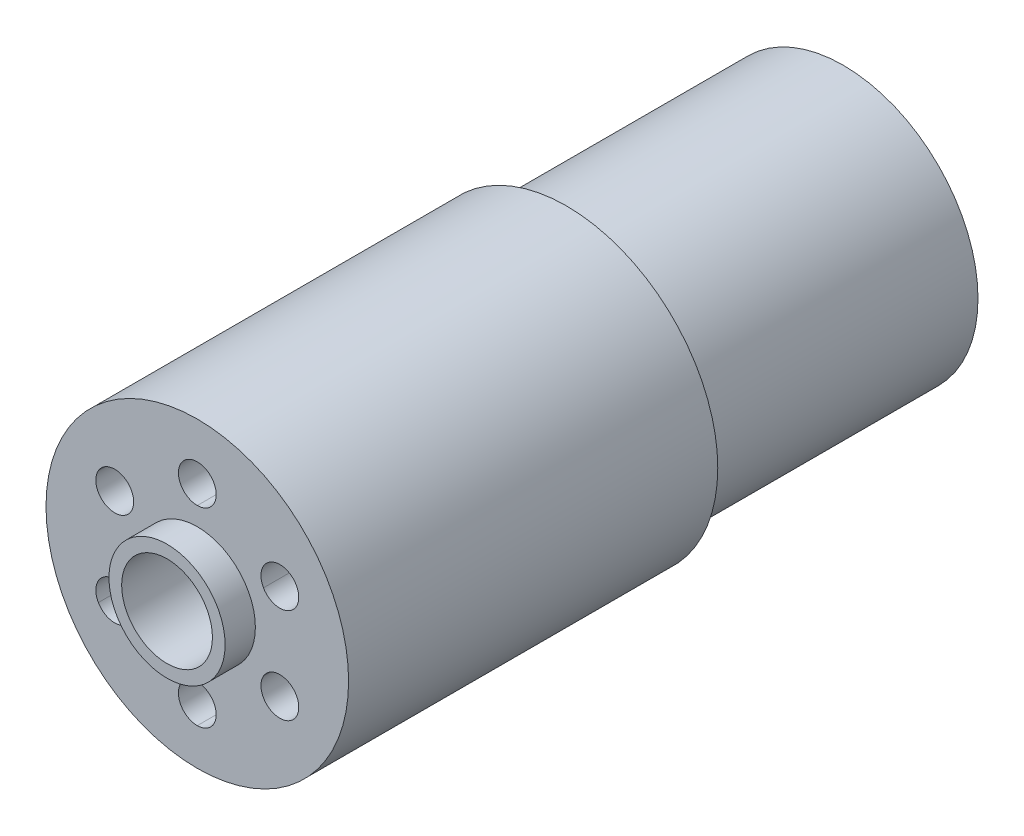
SolidWorks part; units mm, degrees
ref_plane "Front Plane" through (0, 0, 0) normal (0, 0, 1) x (1, 0, 0)
ref_plane "Top Plane" through (0, 0, 0) normal (0, 1, 0) x (1, 0, 0)
ref_plane "Right Plane" through (0, 0, 0) normal (1, 0, 0) x (0, 0, -1)
sketch "Sketch1" plane through (0, 0, 0) normal (0, 0, 1) x (1, 0, 0)
  circle A0 centre (0, 0) radius 25.4
  circle A8 centre (0, 0) radius 9.3953
  point P19 (0, 0)
  dimension "D1" = 50.8
  dimension "D2" = 16.0047
extrude "Boss-Extrude2" add sketch "Sketch1" along normal blind 108.458 contours A0
sketch "Sketch6" plane through (0, 0, 0) normal (0, 0, -1) x (-1, 0, 0)
  circle A0 centre (0, 0) radius 7.62
  circle A1 centre (-13.8581, 8.001) radius 3.175
  circle A2 centre (0, 16.002) radius 3.175
  circle A3 centre (13.8581, 8.001) radius 3.175
  circle A4 centre (13.8581, -8.001) radius 3.175
  circle A5 centre (0, -16.002) radius 3.175
  circle A6 centre (-13.8581, -8.001) radius 3.175
  point P18 (0, 0)
  dimension "D1" = 15.24
  dimension "D2" = 6.35
  dimension "D3" = 16.002
  dimension "D4" = 6
extrude "Cut-Extrude1" cut sketch "Sketch6" against normal blind 108.458
sketch "Sketch7" plane through (0, 0, 0) normal (0, 0, -1) x (-1, 0, 0)
  circle A0 centre (0, 0) radius 22.606
  circle A1 centre (0, 0) radius 25.4 construction
  circle A2 centre (0, 0) radius 25.4
  dimension "D1" = 2.794
extrude "Cut-Extrude2" cut sketch "Sketch7" against normal blind 46.482
sketch "Sketch8" plane through (0, 0, 108.458) normal (0, 0, 1) x (1, 0, 0)
  circle A0 centre (0, 0) radius 7.62
  circle A1 centre (0, 0) radius 9.75
  dimension "D1" = 19.5
  dimension "D2" = 15.24
extrude "Boss-Extrude7" add sketch "Sketch8" along normal blind 5.08
sketch "Sketch9" plane through (0, 0, 0) normal (0, 0, -1) x (-1, 0, 0)
  circle A0 centre (0, 0) radius 7.62
  circle A1 centre (0, 0) radius 9.75
  dimension "D1" = 19.5
  dimension "D2" = 15.24
extrude "Boss-Extrude8" add sketch "Sketch9" along normal blind 5.08
sketch "Sketch10" plane through (0, 0, 0) normal (0, 0, -1) x (-1, 0, 0)
  circle A0 centre (0, 16.002) radius 3.175 construction
  circle A1 centre (0, -16.002) radius 3.175 construction
  circle A2 centre (0, 0) radius 19.177 construction
  circle A3 centre (-13.8581, 8.001) radius 3.175 construction
  circle A4 centre (-13.8581, -8.001) radius 3.175 construction
  circle A5 centre (13.8581, -8.001) radius 3.175 construction
  circle A6 centre (0, 0) radius 12.827 construction
  point P0 (0, 19.177)
  point P1 (0, -19.177)
  point P9 (-16.6078, 9.5885)
  point P10 (-16.6078, -9.5885)
  point P13 (16.6078, -9.5885)
  point P16 (16.6078, 9.5885)
  point P20 (0, 12.827)
  point P21 (-10.9777, 6.6349)
  point P22 (-10.9777, -6.6349)
  point P23 (11.1085, -6.4135)
  point P24 (11.1085, 6.4135)
  point P25 (0, -12.827)
sketch "Sketch11" plane through (0, 0, 108.458) normal (0, 0, 1) x (1, 0, 0)
  point P0 (10.9777, 6.6349)
  point P2 (10.9777, -6.6349)
  point P4 (0, -12.827)
  point P6 (-11.1085, -6.4135)
  point P8 (-11.1085, 6.4135)
  point P10 (0, 12.827)
ref_plane "Plane1" through (0, 0, 0) normal (-1, 0, 0) x (0, 0, 1)
ref_plane "Plane3" through (0, 0, 0) normal (-0.5, -0.866, 0) x (-0.866, 0.5, 0)
ref_plane "Plane6" through (0, 0, 0) normal (0.5, -0.866, 0) x (-0.866, -0.5, 0)
split line "Split Line1"
split line "Split Line2"
split line "Split Line3"
ref_axis "Axis1" through (0, 0, 112.9157) along (0, 0, -1)
